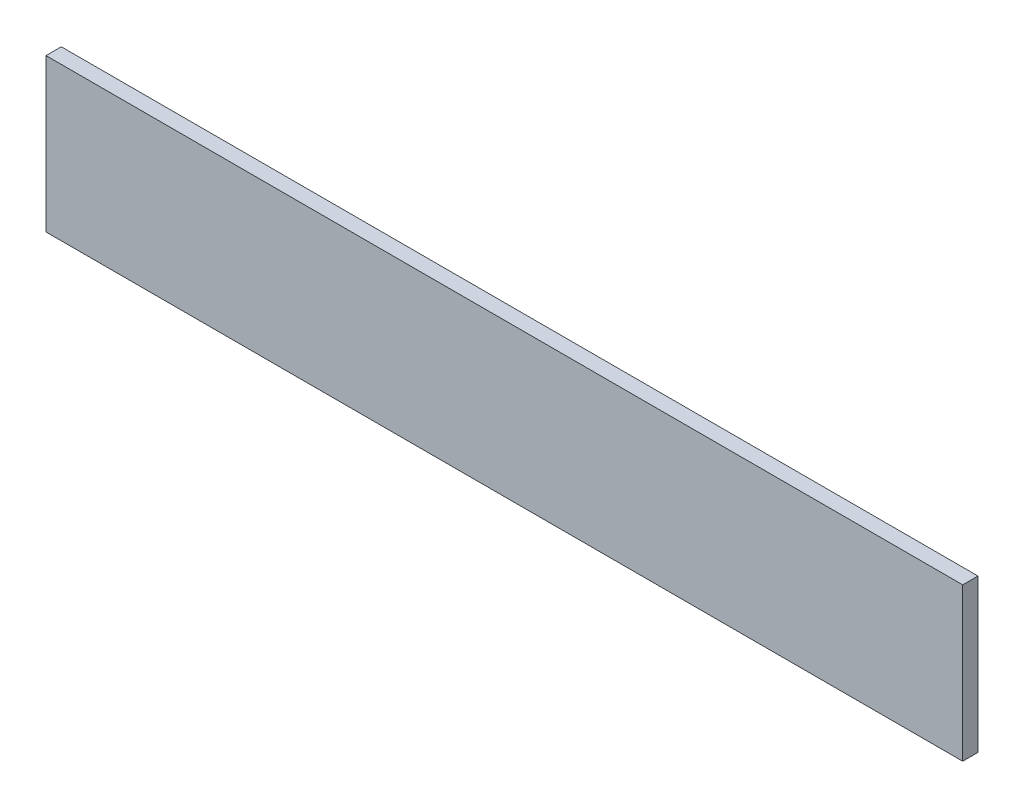
SolidWorks part; units mm, degrees
ref_plane "Спереди" through (0, 0, 0) normal (0, 0, 1) x (1, 0, 0)
ref_plane "Сверху" through (0, 0, 0) normal (0, 1, 0) x (1, 0, 0)
ref_plane "Справа" through (0, 0, 0) normal (1, 0, 0) x (0, 0, -1)
sketch "Эскиз1" plane through (0, 0, 0) normal (0, 0, 1) x (1, 0, 0)
  line L1 (0, 0) -> (120, 0)
  line L2 (0, 0) -> (0, -20)
  line L3 (0, -20) -> (120, -20)
  line L4 (120, 0) -> (120, -20)
extrude "Бобышка-Вытянуть1" add sketch "Эскиз1" along normal blind 2
